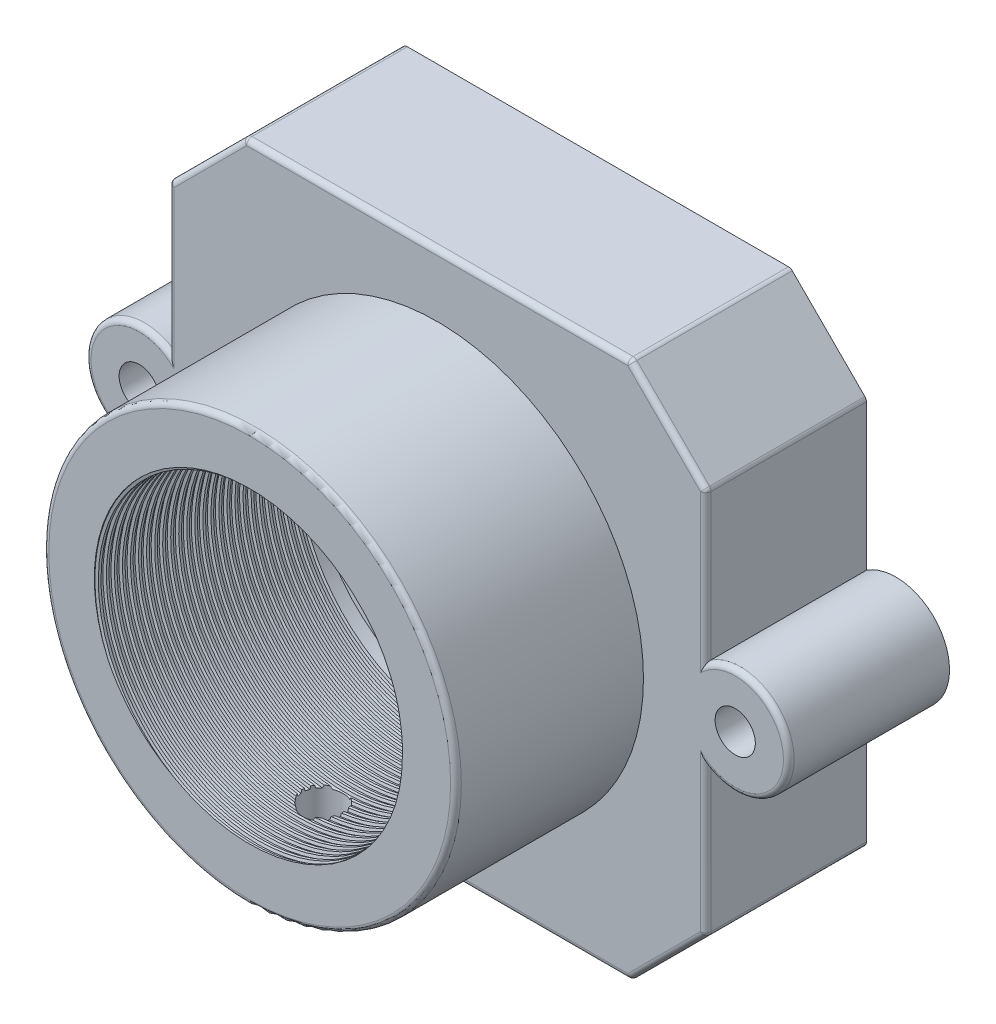
SolidWorks part; units mm, degrees
ref_plane "前视基准面" through (0, 0, 0) normal (0, 0, 1) x (1, 0, 0)
ref_plane "上视基准面" through (0, 0, 0) normal (0, 1, 0) x (1, 0, 0)
ref_plane "右视基准面" through (0, 0, 0) normal (1, 0, 0) x (0, 0, -1)
sketch "草图1" plane through (0, 0, 0) normal (0, 0, 1) x (1, 0, 0)
  line L0 (10.025, -7.1966) -> (7.1966, -10.025)
  line L1 (-7.1966, 10.025) -> (7.1966, 10.025)
  line L2 (-10.025, 7.1966) -> (-10.025, 1.6703)
  line L3 (-7.1966, -10.025) -> (7.1966, -10.025)
  line L4 (10.025, 7.1966) -> (10.025, 1.6703)
  line L5 (-8.6108, 8.6108) -> (8.6108, -8.6108) construction
  line L6 (-8.6108, -8.6108) -> (8.6108, 8.6108) construction
  line L7 (-7.1966, -10.025) -> (-10.025, -7.1966)
  line L8 (-10.025, 7.1966) -> (-7.1966, 10.025)
  line L9 (7.1966, 10.025) -> (10.025, 7.1966)
  line L10 (-10.625, 0) -> (10.925, 0) construction
  line L11 (10.025, -1.6703) -> (10.025, -7.1966)
  line L12 (0, 10.025) -> (0, -10.025) construction
  line L13 (-10.025, -1.6703) -> (-10.025, -7.1966)
  line L14 (-8.825, 6.6995) -> (-8.825, -6.6995)
  line L15 (-8.825, 6.6995) -> (-6.6995, 8.825)
  line L16 (-6.6995, 8.825) -> (6.6995, 8.825)
  line L17 (6.6995, 8.825) -> (8.825, 6.6995)
  line L18 (8.825, 6.6995) -> (8.825, -6.6995)
  line L20 (8.825, -6.6995) -> (6.6995, -8.825)
  line L21 (-6.6995, -8.825) -> (6.6995, -8.825)
  line L22 (-6.6995, -8.825) -> (-8.825, -6.6995)
  line L24 (-8.825, 6.6995) -> (-8.825, 1.6703) construction
  line L25 (-8.825, -1.6703) -> (-8.825, -6.6995) construction
  line L26 (8.825, 6.6995) -> (8.825, 1.6703) construction
  line L27 (8.825, -1.6703) -> (8.825, -6.6995) construction
  arc A0 (10.025, -1.6703) -> (10.025, 1.6703) centre (11.125, 0) ccw
  arc A1 (-10.025, 1.6703) -> (-10.025, -1.6703) centre (-11.125, 0) ccw
  point P0 (0, 0)
  point P17 (0, 0)
  dimension "D2" = 4
  dimension "D5" = 4
  dimension "D1" = 20.05
  dimension "D3" = 4
  dimension "D6" = 1.1
  dimension "D7" = 1.1
  dimension "D8" = 1.2
  dimension "D4" = 4
extrude "凸台-拉伸1" add sketch "草图1" along normal blind 6
sketch "草图2" plane through (0, 0, 0) normal (0, 0, -1) x (-1, 0, 0)
  line L0 (6.6995, 8.825) -> (8.825, 6.6995) construction
  line L1 (-6.6995, 8.825) -> (6.6995, 8.825) construction
  line L2 (-8.825, 6.6995) -> (-6.6995, 8.825) construction
  line L3 (-8.825, -6.6995) -> (-8.825, 6.6995) construction
  line L4 (-6.6995, -8.825) -> (-8.825, -6.6995) construction
  line L5 (6.6995, -8.825) -> (-6.6995, -8.825) construction
  line L6 (8.825, -6.6995) -> (6.6995, -8.825) construction
  line L7 (8.825, 6.6995) -> (8.825, -6.6995) construction
  line L8 (6.6995, 8.825) -> (8.825, 6.6995)
  line L9 (-6.6995, 8.825) -> (6.6995, 8.825)
  line L10 (-8.825, 6.6995) -> (-6.6995, 8.825)
  line L11 (-8.825, -6.6995) -> (-8.825, 6.6995)
  line L12 (-6.6995, -8.825) -> (-8.825, -6.6995)
  line L13 (6.6995, -8.825) -> (-6.6995, -8.825)
  line L14 (8.825, -6.6995) -> (6.6995, -8.825)
  line L15 (8.825, 6.6995) -> (8.825, -6.6995)
  line L16 (-6.8652, 9.225) -> (6.8652, 9.225)
  line L17 (6.8652, 9.225) -> (9.225, 6.8652)
  line L18 (9.225, 6.8652) -> (9.225, -6.8652)
  line L19 (9.225, -6.8652) -> (6.8652, -9.225)
  line L20 (6.8652, -9.225) -> (-6.8652, -9.225)
  line L21 (-6.8652, -9.225) -> (-9.225, -6.8652)
  line L22 (-9.225, -6.8652) -> (-9.225, 6.8652)
  line L23 (-9.225, 6.8652) -> (-6.8652, 9.225)
  dimension "D1" = 0.4
extrude "切除-拉伸1" cut sketch "草图2" against normal blind 1.5
hole_wizard "大小mm 暗销孔1" positions "3D草图1" profile "草图3" hole size "Ø1.5" standard "ISO" end condition through all
sketch3d "3D草图1"
  line L0 (11.125, 0, 6) -> (11.125, 0, 0) construction
  line L1 (-11.125, 0, 6) -> (-11.125, 0, 0) construction
  point P0 (11.125, 0, 0)
  point P4 (-11.125, 0, 0)
sketch "草图3" plane through (11.125, 0, 0) normal (1, 0, 0) x (0, 1, 0)
  line L0 (0, 0) -> (0, 6)
  line L1 (0, 6) -> (0.75, 6)
  line L2 (0.75, 6) -> (0.75, 0)
  line L5 (0.75, 0) -> (0, 0)
  line L11 (0, -6.35) -> (0, 107.95) construction
  dimension "通孔孔直径" = 1.5
  dimension "通孔孔深度" = 6
sketch "草图4" plane through (0, 0, 6) normal (0, 0, 1) x (1, 0, 0)
  line L0 (-8.825, 6.6995) -> (-8.825, -6.6995) construction
  line L1 (-8.825, -6.6995) -> (-6.6995, -8.825) construction
  line L2 (-6.6995, -8.825) -> (6.6995, -8.825) construction
  line L3 (6.6995, -8.825) -> (8.825, -6.6995) construction
  line L4 (8.825, -6.6995) -> (8.825, 6.6995) construction
  line L5 (8.825, 6.6995) -> (6.6995, 8.825) construction
  line L6 (6.6995, 8.825) -> (-6.6995, 8.825) construction
  line L7 (-6.6995, 8.825) -> (-8.825, 6.6995) construction
  line L8 (-8.825, 6.6995) -> (-8.825, -6.6995)
  line L9 (-8.825, -6.6995) -> (-6.6995, -8.825)
  line L10 (-6.6995, -8.825) -> (6.6995, -8.825)
  line L11 (6.6995, -8.825) -> (8.825, -6.6995)
  line L12 (8.825, -6.6995) -> (8.825, 6.6995)
  line L13 (8.825, 6.6995) -> (6.6995, 8.825)
  line L14 (6.6995, 8.825) -> (-6.6995, 8.825)
  line L15 (-6.6995, 8.825) -> (-8.825, 6.6995)
  circle A0 centre (0, 0) radius 5.7
  dimension "D1" = 11.4
extrude "凸台-拉伸2" add sketch "草图4" against normal blind 1
sketch "草图5" plane through (0, 0, 6) normal (0, 0, 1) x (1, 0, 0)
  circle A0 centre (0, 0) radius 7.7
  circle A1 centre (0, 0) radius 5.7
  dimension "D1" = 15.4
  dimension "D2" = 11.4
extrude "凸台-拉伸3" add sketch "草图5" along normal blind 7
hole_wizard "大小mm 暗销孔2" positions "3D草图5" profile "草图10" hole size "Ø1.5" standard "ISO"
sketch3d "3D草图5"
  point P0 (0.0067, -5.7, 10.2703)
  point P3 (0.0067, -5.7, 10.2703)
sketch "草图10" plane through (0.0067, -5.7, 10.2703) normal (0, 0, 1) x (-1, -0.0012, 0)
  line L0 (0, 0) -> (0, 4.3404)
  line L1 (0, 4.3404) -> (0.75, 4.3404)
  line L2 (0.75, 4.3404) -> (0.75, 0)
  line L5 (0.75, 0) -> (0, 0)
  line L11 (0, -6.35) -> (0, 107.95) construction
  dimension "通孔孔直径" = 1.5
  dimension "通孔孔深度" = 4.3404
cosmetic thread "装饰螺纹线3" parameters "D2"=1.8
fillet "圆角1" radius 0.2 21 edges at (7.7, 0, 13) (-8.6108, 8.6108, 6) (0, 10.025, 6) (8.6108, 8.6108, 6) (10.025, 4.4335, 6) (10.025, -4.4335, 6) (8.6108, -8.6108, 6) (-10.025, 4.4335, 6) (-10.025, -4.4335, 6) (-8.6108, -8.6108, 6) (0, -10.025, 6) (-7.1966, 10.025, 3) (-10.025, 7.1966, 3) (7.1966, 10.025, 3) (10.025, 7.1966, 3) (10.025, -7.1966, 3) (7.1966, -10.025, 3) (-10.025, -7.1966, 3) (-7.1966, -10.025, 3) (13.125, 0, 6) (-13.125, 0, 6)
sketch "草图11" plane through (0, 0, 13) normal (0, 0, 1) x (1, 0, 0)
  circle A0 centre (0, 0) radius 5.7
curve "螺旋线/涡状线1" pitch 0.3 height 7.5 turns 25
sketch "草图12" plane through (0, 0, 0) normal (0, 1, 0) x (1, 0, 0)
  line L0 (5.7, -13) -> (5.8, -12.97)
  line L1 (5.8, -12.97) -> (5.8, -12.83)
  line L2 (5.8, -12.83) -> (5.7, -12.8)
  line L3 (5.7, -12.8) -> (5.7, -13)
  dimension "D1" = 0.2
  dimension "D2" = 0.14
  dimension "D3" = 0.1
sweep "切除-扫描1" cut profiles "草图12" path "螺旋线/涡状线1"
